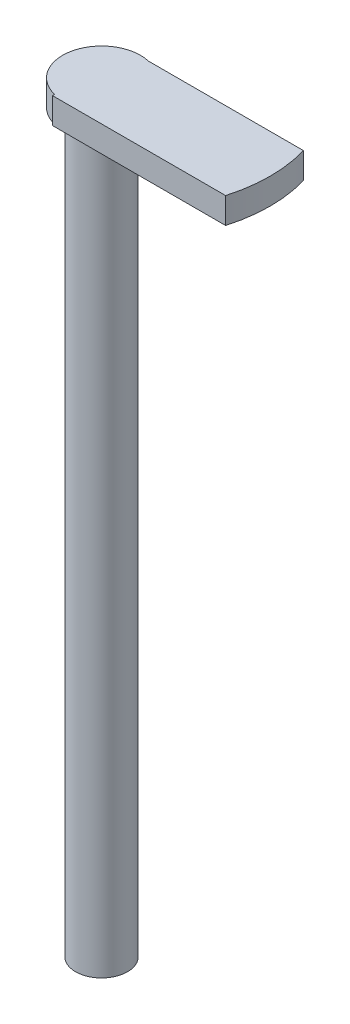
SolidWorks part; units mm, degrees
ref_plane "Front Plane" through (0, 0, 0) normal (0, 0, 1) x (1, 0, 0)
ref_plane "Top Plane" through (0, 0, 0) normal (0, 1, 0) x (1, 0, 0)
ref_plane "Right Plane" through (0, 0, 0) normal (1, 0, 0) x (0, 0, -1)
sketch "Sketch1" plane through (0, 0, 0) normal (0, 1, 0) x (1, 0, 0)
  circle A0 centre (0, 0) radius 3
  dimension "D1" = 6
extrude "Boss-Extrude2" add sketch "Sketch1" along normal blind 85
sketch "Sketch2" plane through (0, 85, 0) normal (0, 1, 0) x (1, 0, 0)
  circle A0 centre (0, 0) radius 4.5
  dimension "D1" = 9
extrude "Boss-Extrude3" add sketch "Sketch2" along normal blind 3
sketch "Sketch3" plane through (0, 88, 0) normal (0, 1, 0) x (1, 0, 0)
  line L1 (-1.042, 4.3777) -> (18.958, 4.3777)
  line L2 (-1.042, 4.3777) -> (-1.042, -4.6223)
  line L3 (-1.042, -4.6223) -> (18.9586, -4.6223)
  circle A0 centre (0, 0) radius 4.5 construction
  arc A1 (18.958, 4.3777) -> (18.9586, -4.6223) centre (3.5583, -0.1233) cw
  dimension "D1" = 9
  dimension "D2" = 20
extrude "Boss-Extrude5" add sketch "Sketch3" against normal blind 3
